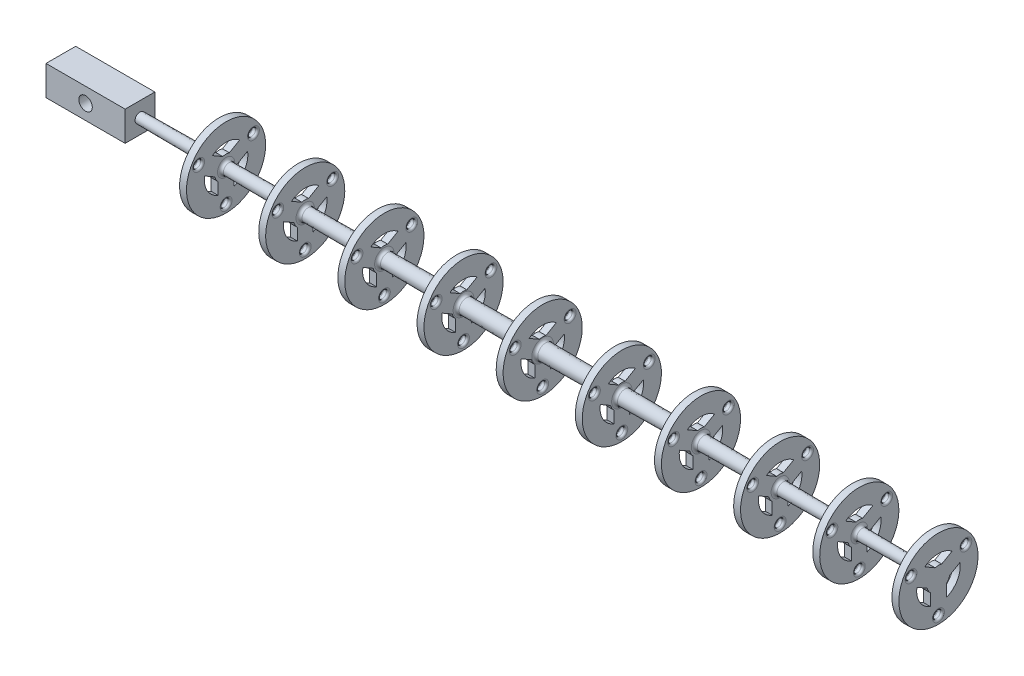
SolidWorks part; units mm, degrees
ref_plane "Front Plane" through (0, 0, 0) normal (0, 0, 1) x (1, 0, 0)
ref_plane "Top Plane" through (0, 0, 0) normal (0, 1, 0) x (1, 0, 0)
ref_plane "Right Plane" through (0, 0, 0) normal (1, 0, 0) x (0, 0, -1)
sketch "Sketch2" plane through (0, 0, 0) normal (0, 0, 1) x (1, 0, 0)
  line L0 (0, 1.25) -> (100, 2)
  line L1 (0, -55) -> (0, 55) construction
  line L3 (100, 0) -> (0, 0)
  line L4 (0, 0) -> (0, 1.25)
  line L6 (200, 1.25) -> (200, 0)
  line L7 (200, 0) -> (100, 0)
  line L8 (100, 0) -> (100, 2) construction
  line L9 (100, 2) -> (200, 1.25)
  dimension "D1" = 1.25
  dimension "D2" = 100
  dimension "D4" = 1.25
  dimension "D3" = 2
  dimension "D5" = 100
revolve "Revolve1" add sketch "Sketch2" angle 360 about L3
ref_axis "Axis1" through (-103.9062, 0, 0) along (1, 0, 0)
sketch "Sketch3" plane through (0, 0, 0) normal (0, 0, 1) x (1, 0, 0)
  line L0 (20, 0) -> (20, 10)
  line L1 (20, 10) -> (21.75, 10)
  line L2 (21.75, 10) -> (21.75, 0)
  line L3 (21.75, 0) -> (20, 0)
  line L4 (0, -11) -> (0, 11) construction
  dimension "D1" = 1.75
  dimension "D2" = 10
  dimension "D3" = 20
revolve "Revolve2" add sketch "Sketch3" angle 360 about L3
sketch "Sketch5" plane through (21.75, 0, 0) normal (1, 0, 0) x (0, 0, -1)
  line L0 (0, -8) -> (0, 0) construction
  line L1 (0, 0) -> (6.9282, 4) construction
  line L2 (-6.9282, 4) -> (0, 0) construction
  line L3 (0, 55) -> (0, -55) construction
  line L4 (-3.4371, 4.2938) -> (-0.8343, 2.7911)
  line L5 (0.8343, 2.7911) -> (3.4371, 4.2938)
  line L6 (2, -2.1181) -> (2, -5.1235)
  line L7 (5.4371, 0.8297) -> (2.8343, -0.673)
  line L8 (-2.8343, -0.673) -> (-5.4371, 0.8297)
  line L9 (-2, -5.1235) -> (-2, -2.1181)
  circle A0 centre (0, -8) radius 1
  circle A1 centre (6.9282, 4) radius 1
  circle A2 centre (-6.9282, 4) radius 1
  arc A3 (-3.4371, 4.2938) -> (3.4371, 4.2938) centre (0, 0) cw
  circle A6 centre (0, 0) radius 10 construction
  arc A8 (-0.8343, 2.7911) -> (0.8343, 2.7911) centre (0, 0) cw
  circle A9 centre (0, 0) radius 1.4131 construction
  arc A10 (5.4371, 0.8297) -> (2, -5.1235) centre (0, 0) cw
  arc A11 (2.8343, -0.673) -> (2, -2.1181) centre (0, 0) cw
  arc A12 (-2, -5.1235) -> (-5.4371, 0.8297) centre (0, 0) cw
  arc A13 (-2, -2.1181) -> (-2.8343, -0.673) centre (0, 0) cw
  point P29 (0, 0)
  dimension "D2" = 2
  dimension "D1" = 8
  dimension "D3" = 120
  dimension "D4" = 120
  dimension "D6" = 2
  dimension "D7" = 4.5
  dimension "D5" = 1.5
  dimension "D8" = 3
extrude "Cut-Extrude1" cut sketch "Sketch5" against normal up to next
fillet "Fillet1" radius 0.5 6 edges at (20, 3, -6.9282) (20, -9, 0) (21.75, -7, 0) (21.75, 5, -6.9282) (20, 3, 6.9282) (21.75, 5, 6.9282)
pattern_linear "LPattern1" count 10 spacing 20 along (1, 0, 0) of "Revolve2", "Cut-Extrude1", "Fillet1"
sketch "Sketch16" plane through (0, 0, 0) normal (-1, 0, 0) x (0, 0, 1)
  line L1 (-3.75, -3.75) -> (3.75, -3.75)
  line L2 (-3.75, -3.75) -> (-3.75, 3.75)
  line L3 (-3.75, 3.75) -> (3.75, 3.75)
  line L4 (3.75, -3.75) -> (3.75, 3.75)
  line L5 (-3.75, -3.75) -> (3.75, 3.75) construction
  line L6 (-3.75, 3.75) -> (3.75, -3.75) construction
  point P0 (0, 0)
  dimension "D1" = 7.5
extrude "Boss-Extrude1" add sketch "Sketch16" along normal blind 20
sketch "Sketch19" plane through (0, 0, -3.75) normal (0, 0, -1) x (-1, 0, 0)
  line L0 (103.9062, 0) -> (-100, 0) construction
  line L1 (20, 3.75) -> (0, 3.75) construction
  line L2 (20, 3.75) -> (20, -3.75) construction
  point P0 (10, 0)
  point P7 (10, 3.75)
  point P10 (20, 0)
hole_wizard "M3 Clearance Hole1" positions "Sketch19" profile "Sketch18" hole size "M3" standard "ANSI Metric" end condition through all
sketch "Sketch18" plane through (-10, 0, -3.75) normal (1, 0, 0) x (0, 1, 0)
  line L0 (0, 0) -> (0, 13.75)
  line L1 (0, 13.75) -> (1.7, 13.75)
  line L2 (1.7, 13.75) -> (1.7, 0.025)
  line L3 (1.7, 0.025) -> (1.725, 0)
  line L5 (1.725, 0) -> (0, 0)
  line L6 (-1.7, 0.025) -> (-1.725, 0) construction
  line L11 (0, -6.35) -> (0, 107.95) construction
  dimension "Thru Hole Dia." = 3.4
  dimension "Thru Hole Depth" = 13.75
  dimension "Near C'Sink Dia." = 3.45
  dimension "Near C'Sink Angle" = 90
fillet "Fillet2" radius 0.75 19 edges at (20, -1.4, 0) (21.75, 1.4131, 0) (40, -1.55, 0) (41.75, 1.5631, 0) (60, -1.7, 0) (61.75, 1.7131, 0) (80, -1.85, 0) (81.75, 1.8631, 0) (100, 2, 0) (200, 1.25, 0) (181.75, 1.3869, 0) (180, -1.4, 0) (161.75, 1.5369, 0) (160, -1.55, 0) (141.75, 1.6869, 0) (140, -1.7, 0) (121.75, 1.8369, 0) (120, -1.85, 0) (101.75, 1.9869, 0)
equation "\"R1\" = 1.25"
equation "\"D1@Sketch2\"=\"R1\""
equation "\"R2\"= 2"
equation "\"L\"=200"
equation "\"disk_thickness\"= 1.75"
equation "\"D1@Sketch3\"=\"disk_thickness\""
equation "\"disk_radius\"= 10"
equation "\"D2@Sketch3\"=\"disk_radius\""
equation "\"disk_spacing_initial\"= 20"
equation "\"D3@Sketch3\"=\"disk_spacing_initial\""
equation "\"tendon_routing_radius\"= 8"
equation "\"D1@Sketch5\"=\"tendon_routing_radius\""
equation "\"tendon_routing_hole_radius\"=2"
equation "\"D2@Sketch5\"=\"tendon_routing_hole_radius\""
equation "\"tendon_routing_hole_fillet\"=0.5"
equation "\"D1@Fillet1\"=\"tendon_routing_hole_fillet\""
equation "\"inter_disk_spacing\"= 20"
equation "\"D3@LPattern1\"=\"inter_disk_spacing\""
equation "\"num_disk\"= 10"
equation "\"D1@LPattern1\"=\"num_disk\""
equation "\"R3\"= 1.25"
equation "\"D4@Sketch2\"=\"R3\""
equation "\"D3@Sketch2\"=\"R2\""
equation "\"D2@Sketch2\"=\"L\"/2"
equation "\"D5@Sketch2\"=\"L\"/2"
